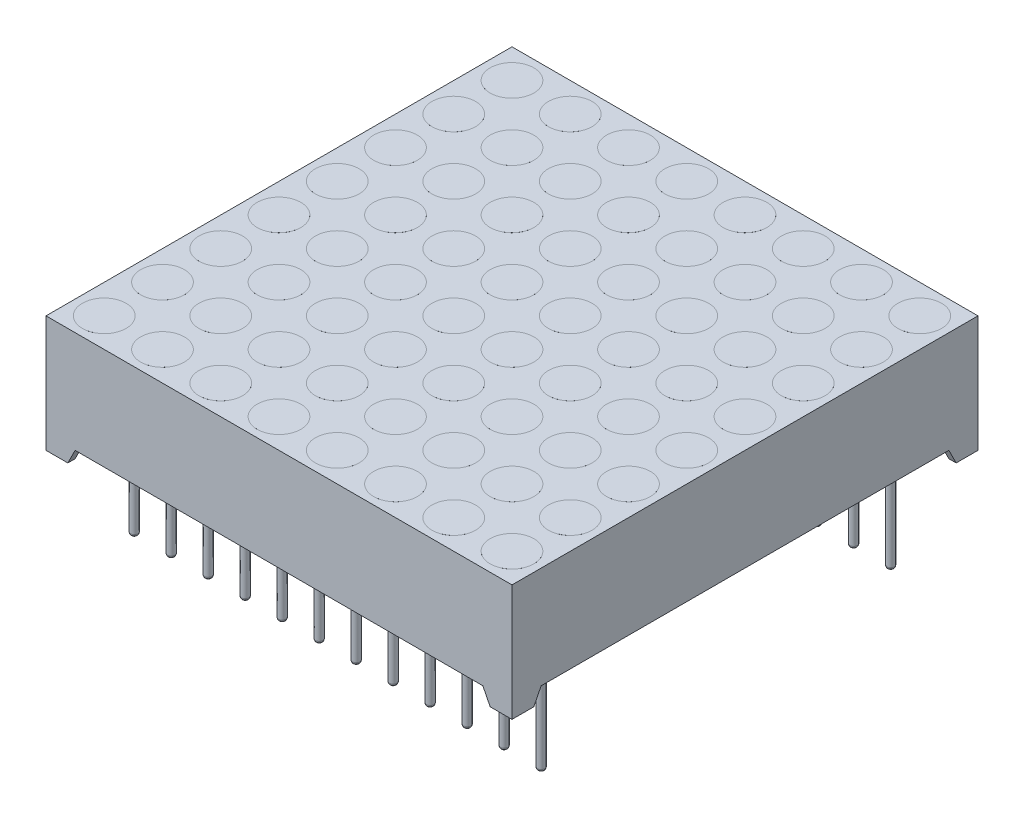
SolidWorks part; units mm, degrees
ref_plane "Front Plane" through (0, 0, 0) normal (0, 0, 1) x (1, 0, 0)
ref_plane "Top Plane" through (0, 0, 0) normal (0, 1, 0) x (1, 0, 0)
ref_plane "Right Plane" through (0, 0, 0) normal (1, 0, 0) x (0, 0, -1)
sketch "Sketch1" plane through (0, 0, 0) normal (0, 1, 0) x (1, 0, 0)
  line L0 (-16, 16) -> (16, -16) construction
  line L1 (-16, 16) -> (16, 16)
  line L2 (-16, 16) -> (-16, -16)
  line L3 (-16, -16) -> (16, -16)
  line L4 (16, 16) -> (16, -16)
  dimension "D1" = 32
extrude "Boss-Extrude1" add sketch "Sketch1" along normal blind 8
shell "Shell1" thickness 0.5 removed face at (0, 0, 0)
sketch "Sketch2" plane through (0, 0, 16) normal (0, 0, 1) x (1, 0, 0)
  line L0 (-14.5, 0) -> (-14, 1)
  line L1 (-14, 1) -> (14, 1)
  line L2 (14, 1) -> (14.5, 0)
  line L3 (14.5, 0) -> (-14.5, 0)
  line L4 (-16, 0) -> (16, 0) construction
  line L5 (0, 0) -> (0, 4.3394) construction
  dimension "D1" = 1
  dimension "D2" = 28
  dimension "D3" = 29
extrude "Cut-Extrude1" cut sketch "Sketch2" against normal through all
ref_axis "Axis1" through (0, 8.4, 0) along (0, -1, 0)
pattern_circular "CirPattern1" count 2 every 90 about axis through (0, 8.4, 0) along (0, -1, 0) of "Cut-Extrude1"
sketch "Sketch3" plane through (0, 8, 0) normal (0, 1, 0) x (-1, 0, 0)
  line L0 (-16, 16) -> (-16, -16) construction
  line L1 (16, 16) -> (-16, 16) construction
  circle A0 centre (-14, 14) radius 1.5
  dimension "D1" = 3
  dimension "D2" = 2
  dimension "D3" = 2
extrude "Boss-Extrude2" add sketch "Sketch3" along normal blind 0.001
pattern_linear "LPattern1" count 8 spacing 4 along (-1, 0, 0) count 8 spacing 4 along (0, 0, -1) of "Boss-Extrude2"
sketch "Sketch4" plane through (0, 7.5, 0) normal (0, -1, 0) x (1, 0, 0)
  line L0 (14, -16) -> (-14, -16) construction
  line L1 (16, 14) -> (16, -14) construction
  circle A0 centre (14, -12) radius 0.25
  dimension "D1" = 0.5
  dimension "D2" = 4
  dimension "D3" = 2
extrude "Boss-Extrude3" add sketch "Sketch4" along normal offset from surface (13.5 mm away) 6 up to face at (15.3333, 0, -15.3333) offset beyond the face yes
fillet "Fillet1" radius 0.2 1 edges at (14, -6, -11.75)
pattern_linear "LPattern2" count 12 spacing 2.54 along (-1, 0, 0) count 2 spacing 24 along (0, 0, 1) of "Boss-Extrude3", "Fillet1"
sketch "Sketch5" plane through (0, 7.5, 0) normal (0, -1, 0) x (1, 0, 0)
  line L4 (-15.5, 15.5) -> (-15.5, -15.5)
  line L5 (-15.5, -15.5) -> (15.5, -15.5)
  line L6 (15.5, -15.5) -> (15.5, 15.5)
  line L7 (15.5, 15.5) -> (-15.5, 15.5)
  line L8 (-15.5, 15.5) -> (-15.5, -15.5)
  line L9 (-15.5, -15.5) -> (15.5, -15.5)
  line L10 (15.5, -15.5) -> (15.5, 15.5)
  line L11 (15.5, 15.5) -> (-15.5, 15.5)
  dimension "D1" = 0
extrude "Boss-Extrude4" add sketch "Sketch5" along normal blind 5
fillet "Fillet2" radius 1 4 edges at (0, 2.5, -15.5) (15.5, 2.5, 0) (0, 2.5, 15.5) (-15.5, 2.5, 0)
